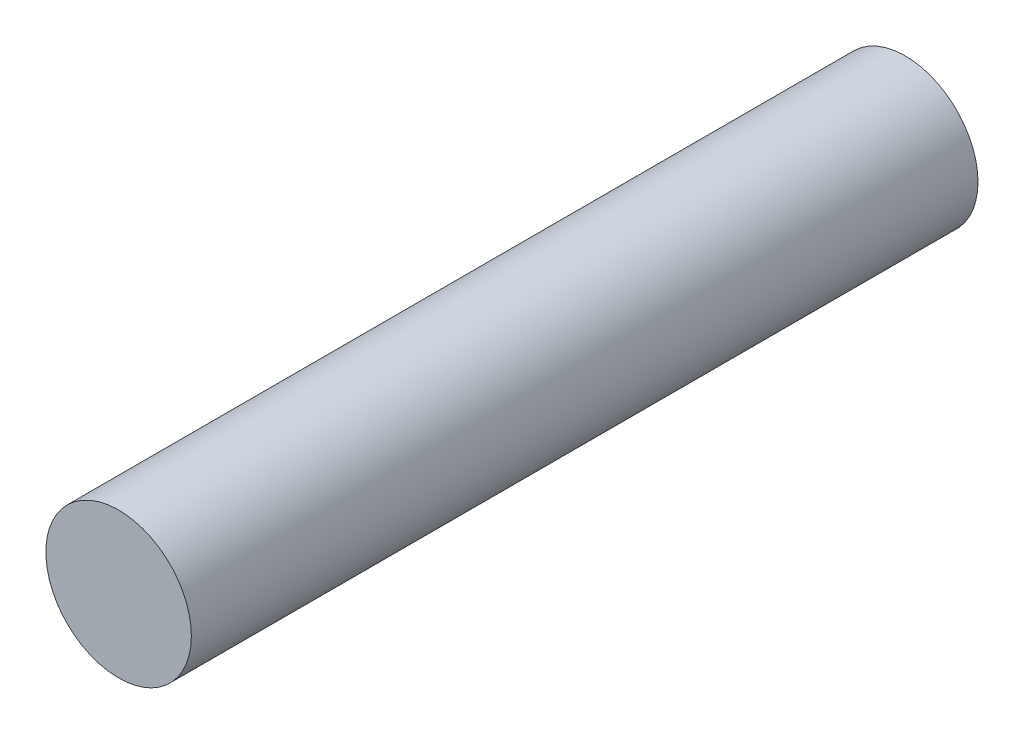
SolidWorks part; units mm, degrees
ref_plane "Front Plane" through (0, 0, 0) normal (0, 0, 1) x (1, 0, 0)
ref_plane "Top Plane" through (0, 0, 0) normal (0, 1, 0) x (1, 0, 0)
ref_plane "Right Plane" through (0, 0, 0) normal (1, 0, 0) x (0, 0, -1)
sketch "Sketch1" plane through (0, 0, 0) normal (0, 0, 1) x (1, 0, 0)
  circle A0 centre (0, 0) radius 75
  dimension "D1" = 150
extrude "Boss-Extrude1" add sketch "Sketch1" along normal blind 811
